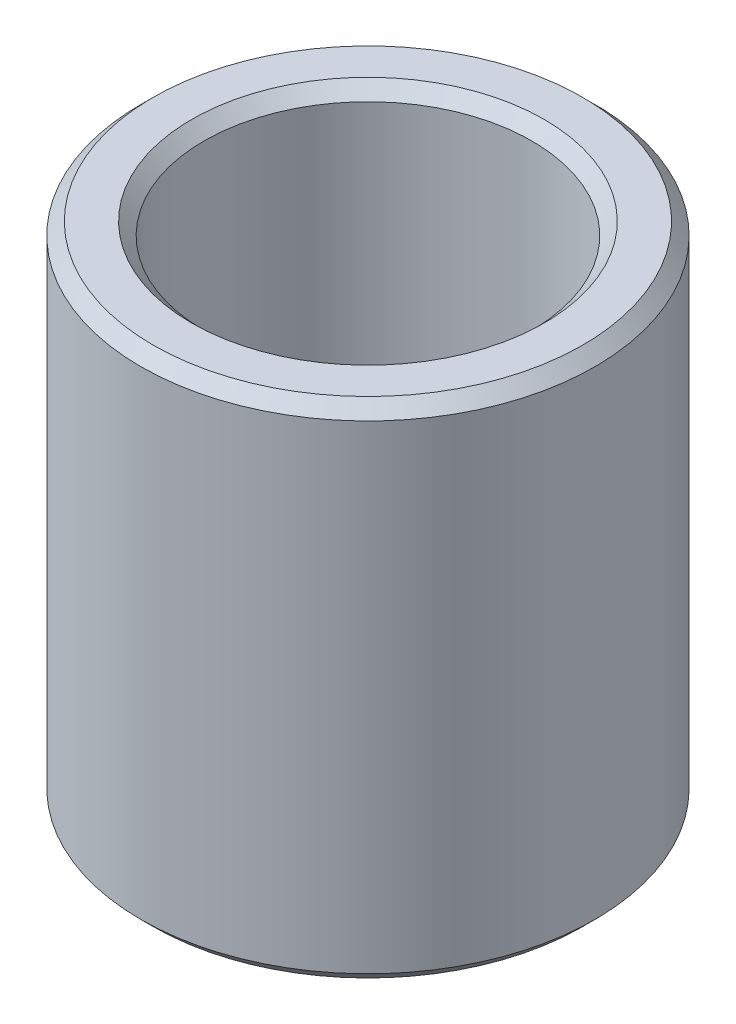
SolidWorks part; units mm, degrees
ref_plane "Front Plane" through (0, 0, 0) normal (0, 0, 1) x (1, 0, 0)
ref_plane "Top Plane" through (0, 0, 0) normal (0, 1, 0) x (1, 0, 0)
ref_plane "Right Plane" through (0, 0, 0) normal (1, 0, 0) x (0, 0, -1)
sketch "Sketch1" plane through (0, 0, 0) normal (0, 1, 0) x (1, 0, 0)
  circle A0 centre (0, 0) radius 50
  dimension "SLEEVE_OD" = 100
extrude "Boss-Extrude1" add sketch "Sketch1" along normal blind 110.8684
sketch "Sketch2" plane through (0, 0, 0) normal (0, 1, 0) x (1, 0, 0)
  circle A0 centre (0, 0) radius 36.092
  dimension "BORE_D" = 72.1839
extrude "Cut-Extrude1" cut sketch "Sketch2" along normal through all
chamfer "Chamfer1" distance 2.7315 angle 45 4 edges at (0, 110.8684, 36.092) (0, 0, 36.092) (0, 0, 50) (0, 110.8684, 50)
